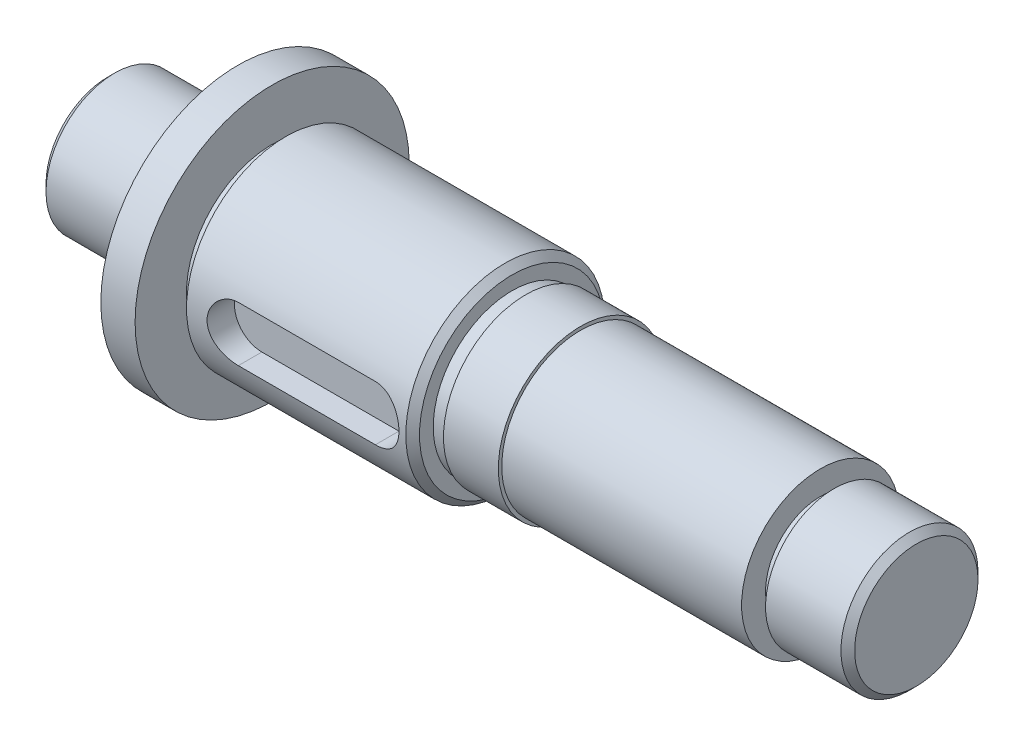
SolidWorks part; units mm, degrees
ref_plane "前视基准面" through (0, 0, 0) normal (0, 0, 1) x (1, 0, 0)
ref_plane "上视基准面" through (0, 0, 0) normal (0, 1, 0) x (1, 0, 0)
ref_plane "右视基准面" through (0, 0, 0) normal (1, 0, 0) x (0, 0, -1)
other "Configuration Table"
sketch "草图1" plane through (0, 0, 0) normal (0, 0, 1) x (1, 0, 0)
  line L0 (0, 0) -> (-26.4759, 0) construction
  line L1 (0, 0) -> (0, 10)
  line L2 (0, 10) -> (12, 10)
  line L3 (12, 10) -> (12, 8)
  line L4 (12, 8) -> (14, 8)
  line L5 (14, 8) -> (14, 12.5)
  line L6 (14, 12.5) -> (19, 12.5)
  line L7 (19, 12.5) -> (19, 20)
  line L8 (19, 20) -> (24, 20)
  line L9 (24, 20) -> (24, 12.5)
  line L10 (24, 12.5) -> (26, 12.5)
  line L11 (26, 12.5) -> (26, 14.5)
  line L12 (26, 14.5) -> (59, 14.5)
  line L13 (59, 14.5) -> (59, 11.5)
  line L14 (59, 11.5) -> (61, 11.5)
  line L15 (61, 11.5) -> (61, 12)
  line L16 (61, 12) -> (69, 12)
  line L17 (69, 12) -> (69, 11.5)
  line L18 (69, 11.5) -> (104, 11.5)
  line L19 (104, 11.5) -> (104, 8)
  line L20 (104, 8) -> (106, 8)
  line L21 (106, 8) -> (106, 10)
  line L22 (106, 10) -> (118, 10)
  line L23 (118, 10) -> (118, 0)
  line L24 (0, 0) -> (118, 0)
  point P27 (66.2643, 0.5566)
  dimension "D1" = 20
  dimension "D2" = 40
  dimension "D3" = 24
  dimension "D4" = 23
  dimension "D5" = 20
  dimension "D6" = 14
  dimension "D7" = 2
  dimension "D8" = 10
  dimension "D9" = 5
  dimension "D10" = 29
  dimension "D11" = 118
  dimension "D12" = 90
  dimension "D13" = 2
  dimension "D14" = 2
  dimension "D15" = 10
  dimension "D16" = 2
  dimension "D17" = 2
  dimension "D18" = 25
  dimension "D19" = 2
  dimension "D20" = 35
revolve "旋转1" add sketch "草图1" angle 360 about L0
chamfer "倒角1" distance 1 angle 45 3 edges at (59, 0, -14.5) (118, 0, -10) (0, 0, -10)
ref_plane "基准面1" through (29, 0, 0) normal (1, 0, 0) x (0, 0, -1)
sketch "草图2" plane through (29, 0, 0) normal (1, 0, 0) x (0, 0, -1)
  line L1 (-16.016, 4) -> (-10.5, 4)
  line L2 (-16.016, 4) -> (-16.016, -4)
  line L3 (-16.016, -4) -> (-10.5, -4)
  line L4 (-10.5, 4) -> (-10.5, -4)
  line L5 (-16.016, 4) -> (-10.5, -4) construction
  line L6 (-16.016, -4) -> (-10.5, 4) construction
  circle A2 centre (0, 0) radius 14.5 construction
  point P0 (-13.258, 0)
  point P5 (0, 0)
  dimension "D1" = 25
  dimension "D2" = 8
extrude "切除-拉伸1" cut sketch "草图2" along normal blind 28
fillet "圆角1" 2 edges at (29, 4, 12.2187) (29, -4, 12.2187) type full round first side face at (43, 4, 12.2187) second side face at (43, -4, 12.2187) middle face at (29, 0, 12.3593)
fillet "圆角2" 2 edges at (57, 4, 12.2187) (57, -4, 12.2187) type full round first side face at (45, 4, 12.2187) second side face at (45, -4, 12.2187) middle face at (57, 0, 12.3593)
